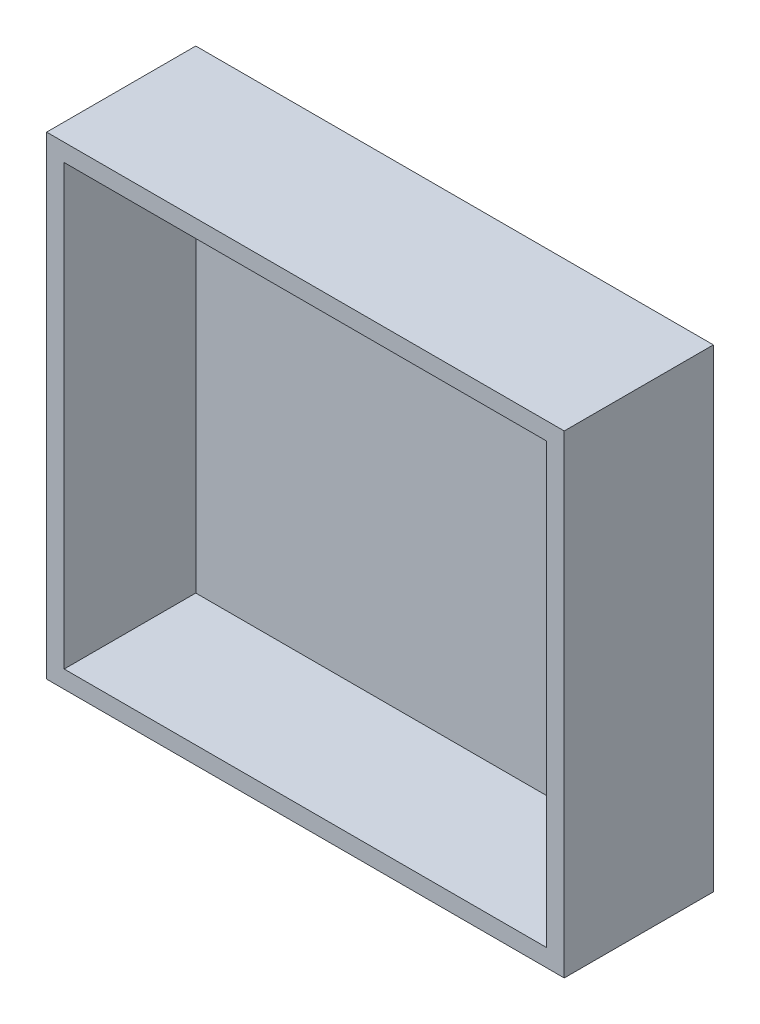
SolidWorks part; units mm, degrees
ref_plane "Plan de face" through (0, 0, 0) normal (0, 0, 1) x (1, 0, 0)
ref_plane "Plan de dessus" through (0, 0, 0) normal (0, 1, 0) x (1, 0, 0)
ref_plane "Plan de droite" through (0, 0, 0) normal (1, 0, 0) x (0, 0, -1)
sketch "Esquisse1" plane through (0, 0, 0) normal (0, 0, 1) x (1, 0, 0)
  line L0 (-8, 208) -> (228, 208)
  line L1 (0, 0) -> (220, 0)
  line L2 (0, 0) -> (0, 200)
  line L3 (0, 200) -> (220, 200)
  line L4 (220, 0) -> (220, 200)
  line L5 (228, -8) -> (228, 208)
  line L6 (-8, -8) -> (228, -8)
  line L7 (-8, -8) -> (-8, 208)
  dimension "D1" = 200
  dimension "D2" = 220
  dimension "D3" = 8
extrude "Boss.-Extru.3" add sketch "Esquisse1" along normal blind 60
extrude "Boss.-Extru.4" add sketch "Esquisse1<2>" against normal blind 8 contours L1 L4 L3 L2 | L7 L6 L5 L0 L4 L1 L2 L3 region at (110, 204.8008, 0) region at (110, 100, 0)
sketch "Esquisse1<2>" plane through (0, 0, 0) normal (0, 0, 1) x (1, 0, 0) same geometry as "Esquisse1"
